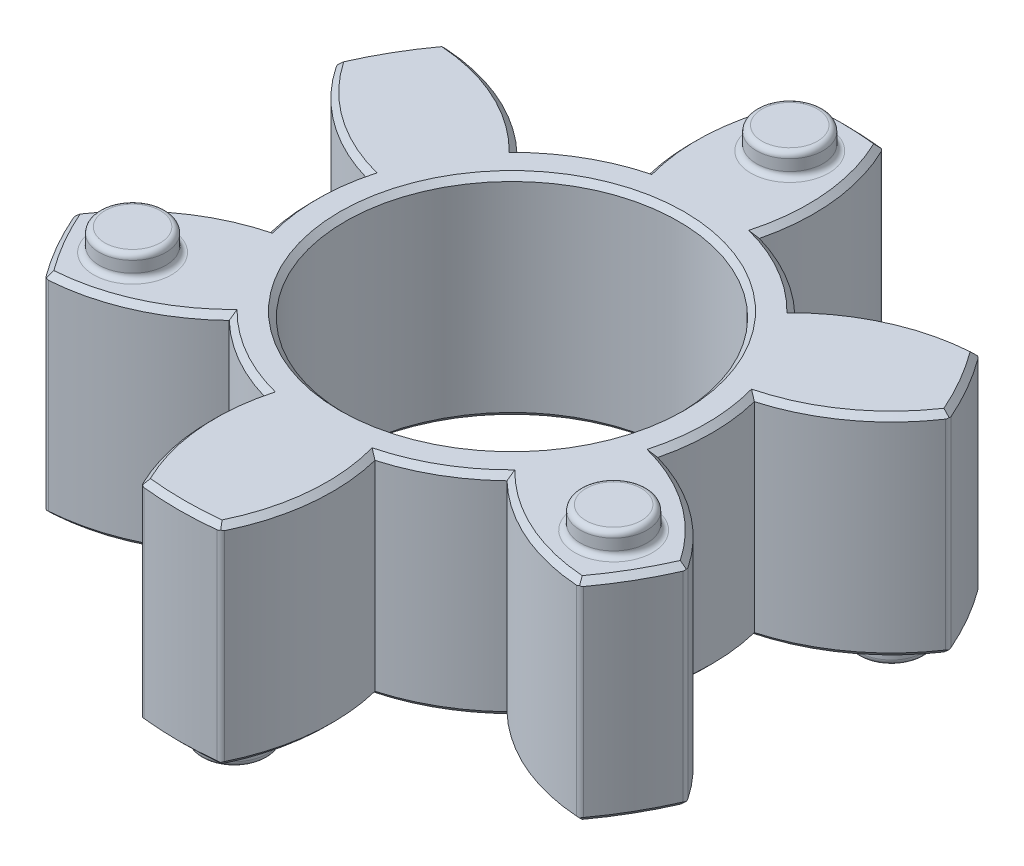
SolidWorks part; units mm, degrees
material "Polyurethane Foam Rigid"
ref_plane "Front Plane" through (0, 0, 0) normal (0, 0, 1) x (1, 0, 0)
ref_plane "Top Plane" through (0, 0, 0) normal (0, 1, 0) x (1, 0, 0)
ref_plane "Right Plane" through (0, 0, 0) normal (1, 0, 0) x (0, 0, -1)
sketch "Body Sketch" plane through (0, 0, 0) normal (0, 1, 0) x (1, 0, 0)
  circle A0 centre (0, 0) radius 15
  dimension "D" = 30
extrude "Body" add sketch "Body Sketch" along normal mid plane 9.5
sketch "Body Hole Sketch" plane through (0, 0, 0) normal (0, 1, 0) x (1, 0, 0)
  circle A0 centre (0, 0) radius 7.5
  dimension "d1" = 15
extrude "Body Hole" cut sketch "Body Hole Sketch" along normal through all both and the other way through all
sketch "Leg Skech" plane through (0, 0, 0) normal (0, 1, 0) x (1, 0, 0)
  arc A0 (-2.4833, 8.6506) -> (-6.25, 6.4759) centre (0, 0) ccw
  arc A1 (14.9833, 8.6506) -> (6.25, 6.4759) centre (12.5, 0) ccw
  arc A2 (14.9833, -8.6506) -> (8.7333, -2.1747) centre (6.25, -10.8253) ccw
  arc A3 (0, -17.3012) -> (2.4833, -8.6506) centre (-6.25, -10.8253) ccw
  arc A4 (-14.9833, -8.6506) -> (-6.25, -6.4759) centre (-12.5, 0) ccw
  arc A5 (-14.9833, 8.6506) -> (-8.7333, 2.1747) centre (-6.25, 10.8253) ccw
  arc A6 (0, 17.3012) -> (-2.4833, 8.6506) centre (6.25, 10.8253) ccw
  arc A7 (2.4833, 8.6506) -> (0, 17.3012) centre (-6.25, 10.8253) ccw
  arc A8 (8.7333, 2.1747) -> (14.9833, 8.6506) centre (6.25, 10.8253) ccw
  arc A9 (6.25, -6.4759) -> (14.9833, -8.6506) centre (12.5, 0) ccw
  arc A10 (-2.4833, -8.6506) -> (0, -17.3012) centre (6.25, -10.8253) ccw
  arc A11 (-6.25, 6.4759) -> (-14.9833, 8.6506) centre (-12.5, 0) ccw
  arc A12 (-8.7333, -2.1747) -> (-14.9833, -8.6506) centre (-6.25, -10.8253) ccw
  arc A13 (-8.7333, 2.1747) -> (-8.7333, -2.1747) centre (0, 0) ccw
  arc A14 (-6.25, -6.4759) -> (-2.4833, -8.6506) centre (0, 0) ccw
  arc A15 (2.4833, -8.6506) -> (6.25, -6.4759) centre (0, 0) ccw
  arc A16 (8.7333, -2.1747) -> (8.7333, 2.1747) centre (0, 0) ccw
  arc A17 (6.25, 6.4759) -> (2.4833, 8.6506) centre (0, 0) ccw
  point P17 (0, 0)
  dimension "D1" = 18
  dimension "D3" = 12.5
  dimension "D4" = 12.5
  dimension "D2" = 6
extrude "Legs" cut sketch "Leg Skech" along normal through all both and the other way through all flip side to cut
chamfer "Aesthetic Chamfer" distance 0.25 angle 45 50 edges at (0, 4.75, 15) (-2.6931, 4.75, 11.836) (-4.5, 4.75, 7.7942) (-8.9038, 4.75, 8.2503) (-12.9904, 4.75, 7.5) (-11.5968, 4.75, 3.5858) (-9, 4.75, 0) (-11.5968, 4.75, -3.5858) (-12.9904, 4.75, -7.5) (-8.9038, 4.75, -8.2503) (-4.5, 4.75, -7.7942) (-2.6931, 4.75, -11.836) (0, 4.75, -15) (2.6931, 4.75, -11.836) (4.5, 4.75, -7.7942) (8.9038, 4.75, -8.2503) (12.9904, 4.75, -7.5) (11.5968, 4.75, -3.5858) (9, 4.75, 0) (11.5968, 4.75, 3.5858) (12.9904, 4.75, 7.5) (8.9038, 4.75, 8.2503) (4.5, 4.75, 7.7942) (2.6931, 4.75, 11.836) (0, 4.75, 7.5) (8.9038, -4.75, 8.2503) (12.9904, -4.75, 7.5) (11.5968, -4.75, 3.5858) (9, -4.75, 0) (11.5968, -4.75, -3.5858) (12.9904, -4.75, -7.5) (8.9038, -4.75, -8.2503) (4.5, -4.75, -7.7942) (2.6931, -4.75, -11.836) (0, -4.75, -15) (-2.6931, -4.75, -11.836) (-4.5, -4.75, -7.7942) (-8.9038, -4.75, -8.2503) (-12.9904, -4.75, -7.5) (-11.5968, -4.75, -3.5858) (-9, -4.75, 0) (-11.5968, -4.75, 3.5858) (-12.9904, -4.75, 7.5) (-8.9038, -4.75, 8.2503) (-4.5, -4.75, 7.7942) (-2.6931, -4.75, 11.836) (0, -4.75, 15) (2.6931, -4.75, 11.836) (4.5, -4.75, 7.7942) (0, -4.75, 7.5)
sketch "Top Distance Sketch" plane through (0, 0, 0) normal (0, 1, 0) x (1, 0, 0)
  circle A0 centre (0, 12.5) radius 1.5
  circle A1 centre (10.8253, -6.25) radius 1.5
  circle A2 centre (-10.8253, -6.25) radius 1.5
  point P10 (0, 0)
  dimension "D1" = 3
  dimension "D2" = 12.5
  dimension "D3" = 3
extrude "Top Distance" add sketch "Top Distance Sketch" along normal blind 1 from surface starting at face at (0, 4.75, 0)
sketch "Bottom Distance Sketch" plane through (0, 0, 0) normal (0, 1, 0) x (1, 0, 0)
  circle A0 centre (0, -12.5) radius 1.5
  circle A1 centre (-10.8253, 6.25) radius 1.5
  circle A2 centre (10.8253, 6.25) radius 1.5
  point P9 (0, 0)
  dimension "D1" = 3
  dimension "D2" = 12.5
  dimension "D3" = 3
extrude "Bottom Distance" add sketch "Bottom Distance Sketch" against normal blind 1 from surface starting at face at (0, -4.75, 0)
fillet "Aesthetic Fillet" radius 0.25 24 edges at (12.01, 0, 8.9867) (13.7877, 0, 5.9076) (13.7877, 0, -5.9076) (12.01, 0, -8.9867) (1.7777, 0, -14.8943) (-1.7777, 0, -14.8943) (-12.01, 0, -8.9867) (-13.7877, 0, -5.9076) (-13.7877, 0, 5.9076) (-12.01, 0, 8.9867) (-1.7777, 0, 14.8943) (1.7777, 0, 14.8943) (0, 4.75, -11) (0, 5.75, -11) (10.8253, 4.75, 7.75) (10.8253, 5.75, 7.75) (-10.8253, 4.75, 7.75) (-10.8253, 5.75, 7.75) (-10.8253, -4.75, -4.75) (-10.8253, -5.75, -4.75) (10.8253, -4.75, -4.75) (10.8253, -5.75, -4.75) (0, -4.75, 14) (0, -5.75, 14)
equation "\"L\"= 35.00"
equation "\"L2@Body\"= ( 2 * ( \"L\" - 0.5 ) / 6 ) - 2'Body Length"
equation "\"d1@Body Hole Sketch\"= \"D@Body Sketch\" / 2'Body Hole Diameter"
equation "\"D1@Leg Skech\"= \"D@Body Sketch\" * 0.6"
equation "\"D3@Leg Skech\"= 0.5 + \"D@Body Sketch\" * 0.4'Jaw Radius"
equation "\"D4@Leg Skech\" = 0.5 + \"D@Body Sketch\" * 0.4'Jaw Radius"
equation "\"D1@Top Distance Sketch\"= \"D@Body Sketch\" / 10'Distance Radius"
equation "\"D2@Top Distance Sketch\"= 0.5 + \"D@Body Sketch\" * 0.4'Distance Position"
equation "\"D1@Bottom Distance Sketch\"= \"D@Body Sketch\" / 10'Distance Radius"
equation "\"D2@Bottom Distance Sketch\"= 0.5 + \"D@Body Sketch\" * 0.4'Distance Position"
equation "\"D3@Top Distance Sketch\"= \"D2@Leg Skech\" / 2'Number of Top Distances"
equation "\"D3@Bottom Distance Sketch\"= \"D2@Leg Skech\" / 2'Number of Bottom Distances"
